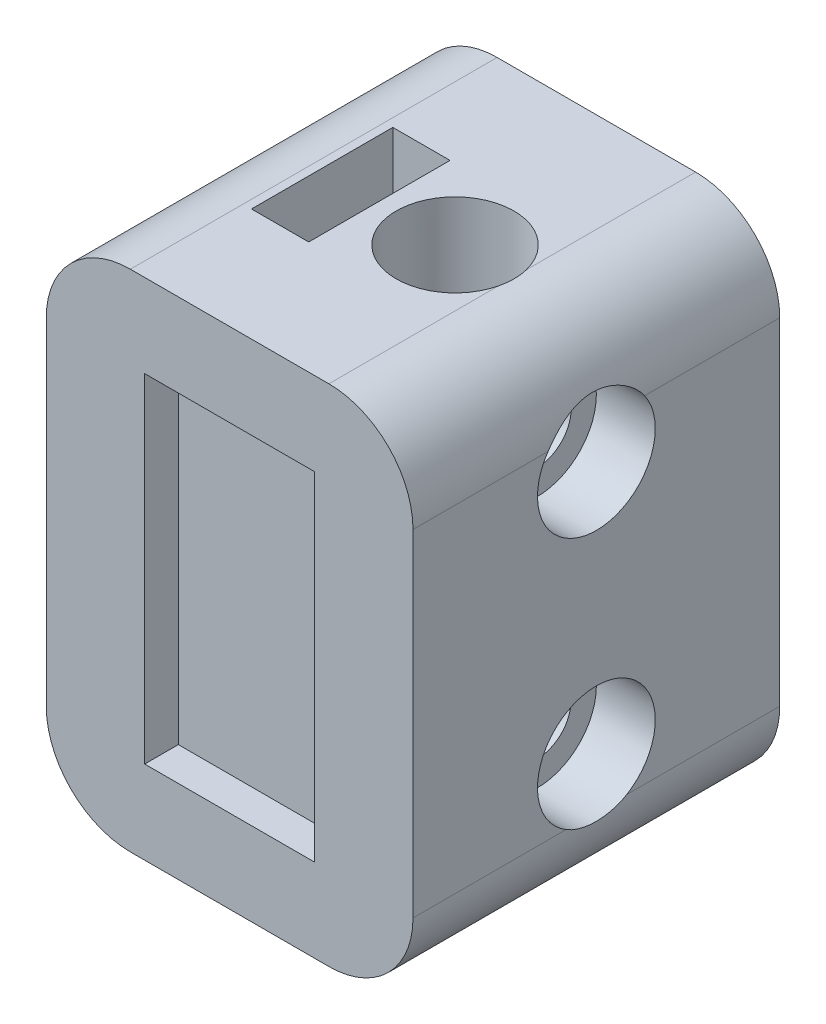
SolidWorks part; units mm, degrees
ref_plane "Alzado" through (0, 0, 0) normal (0, 0, 1) x (1, 0, 0)
ref_plane "Planta" through (0, 0, 0) normal (0, 1, 0) x (1, 0, 0)
ref_plane "Vista lateral" through (0, 0, 0) normal (1, 0, 0) x (0, 0, -1)
sketch "Croquis1" plane through (0, 0, 0) normal (1, 0, 0) x (0, 0, -1)
  line L1 (0, 0) -> (-21.8, 0)
  line L2 (0, 0) -> (0, -30)
  line L3 (0, -30) -> (-21.8, -30)
  line L4 (-21.8, 0) -> (-21.8, -30)
  dimension "D1" = 21.8
  dimension "D2" = 30
extrude "Saliente-Extruir1" add sketch "Croquis1" along normal blind 21.8 contours L2 L3 L4 L1
sketch "Croquis6" plane through (0, 0, 0) normal (-1, 0, 0) x (0, 0, 1)
  line L1 (10.9, -7) -> (10.9, 0) construction
  line L2 (10.9, -22) -> (10.9, -7) construction
  line L3 (0, 0) -> (21.8, 0) construction
  circle A0 centre (10.9, -22) radius 2
  circle A1 centre (10.9, -7) radius 2
  dimension "D1" = 15
  dimension "D3" = 4
  dimension "D4" = 4
  dimension "D2" = 7
extrude "Cortar-Extruir2" cut sketch "Croquis6" against normal up to surface (21.8 mm away) up to face at (21.8, -15, 10.9)
sketch "Croquis7" plane through (21.8, 0, 0) normal (1, 0, 0) x (0, 0, -1)
  line L2 (-10.9, -22) -> (-10.9, -7) construction
  circle A0 centre (-10.9, -22) radius 3.5
  circle A1 centre (-10.9, -7) radius 3.5
  circle A2 centre (-10.9, -7) radius 2 construction
  dimension "D1" = 7
  dimension "D2" = 7
  dimension "D3" = 15
sketch "Croquis11" plane through (0, -30, 0) normal (0, -1, 0) x (1, 0, 0)
  line L0 (13.4, 5.9) -> (13.4, 10.9) construction
  line L1 (0, 0) -> (0, 21.8) construction
  line L2 (0, 0) -> (0, 21.8) construction
  line L7 (16.9, 10.9) -> (21.8, 10.9) construction
  line L8 (13.4, 10.9) -> (8.9, 10.9) construction
  line L9 (8.9, 15.1) -> (5.5, 15.1)
  line L14 (8.9, 15.1) -> (8.9, 6.7)
  line L16 (8.9, 6.7) -> (5.5, 6.7)
  line L17 (5.5, 15.1) -> (5.5, 6.7)
  line L18 (21.8, 0) -> (21.8, 21.8) construction
  line L19 (5.5, 10.9) -> (0, 10.9) construction
  circle A1 centre (13.4, 10.9) radius 3.5
  dimension "D1" = 8.4
  dimension "D2" = 5.5
  dimension "D3" = 5
  dimension "D4" = 3.4
  dimension "D5" = 4.5
extrude "Cortar-Extruir4" cut sketch "Croquis11" against normal up to surface (30 mm away) and the other way blind 3.5 contours A1 | L14 L9 L17 L16 up to face at (10.9, 0, 10.9)
fillet "Redondeo1" radius 5 4 edges at (21.8, -30, 10.9) (0, -30, 10.9) (21.8, 0, 10.9) (0, 0, 10.9)
sketch "Croquis13" plane through (0, 0, 0) normal (-1, 0, 0) x (0, 0, 1)
  line L0 (10.9, -7) -> (10.9, -22) construction
  line L1 (10.9, -14.5) -> (2.8317, -14.5) construction
  circle A0 centre (10.9, -22) radius 2 construction
  circle A1 centre (10.9, -7) radius 2 construction
  circle A2 centre (10.9, -22) radius 2 construction
  circle A3 centre (10.9, -7) radius 2 construction
  circle A4 centre (10.9, -7) radius 3.5
  circle A5 centre (10.9, -22) radius 3.5
  dimension "D1" = 7
extrude "Cortar-Extruir6" cut sketch "Croquis13" against normal blind 3.5
sketch "Croquis16" plane through (0, 0, 21.8) normal (0, 0, 1) x (1, 0, 0)
  line L0 (10.9, 0) -> (10.9, -4.95) construction
  line L1 (16.8, 0) -> (5, 0) construction
  line L2 (10.9, -4.95) -> (5.85, -4.95) construction
  line L3 (10.9, -25.05) -> (10.9, -30) construction
  line L4 (5.85, -4.95) -> (15.95, -4.95)
  line L5 (5.85, -4.95) -> (5.85, -25.05)
  line L6 (5.85, -25.05) -> (15.95, -25.05)
  line L7 (15.95, -4.95) -> (15.95, -25.05)
  line L8 (16.8, -30) -> (5, -30) construction
  line L11 (15.95, -15) -> (21.8, -15) construction
  line L12 (21.8, -5) -> (21.8, -25) construction
  line L13 (0, -5) -> (0, -25) construction
  line L14 (5.85, -15) -> (0, -15) construction
  point P16 (0, 0)
  point P17 (10.9, -4.95)
  point P18 (0, 0)
  point P21 (0, 0)
  dimension "D2" = 10.1
  dimension "D3" = 20.1
  dimension "D4" = 4.95
extrude "Cortar-Extruir7" cut sketch "Croquis16" against normal blind 2
sketch "Croquis17" plane through (0, 0, 0) normal (0, 0, -1) x (-1, 0, 0)
  line L4 (-15.95, -25.05) -> (-15.95, -4.95) construction
  line L5 (-15.95, -4.95) -> (-5.85, -4.95) construction
  line L6 (-5.85, -4.95) -> (-5.85, -25.05) construction
  line L7 (-5.85, -25.05) -> (-15.95, -25.05) construction
  line L12 (-15.95, -25.05) -> (-15.95, -4.95)
  line L13 (-15.95, -4.95) -> (-5.85, -4.95)
  line L14 (-5.85, -4.95) -> (-5.85, -25.05)
  line L15 (-5.85, -25.05) -> (-15.95, -25.05)
extrude "Cortar-Extruir8" cut sketch "Croquis17" against normal blind 2
extrude "Cortar-Extruir9" cut sketch "Croquis7" against normal blind 3.5
